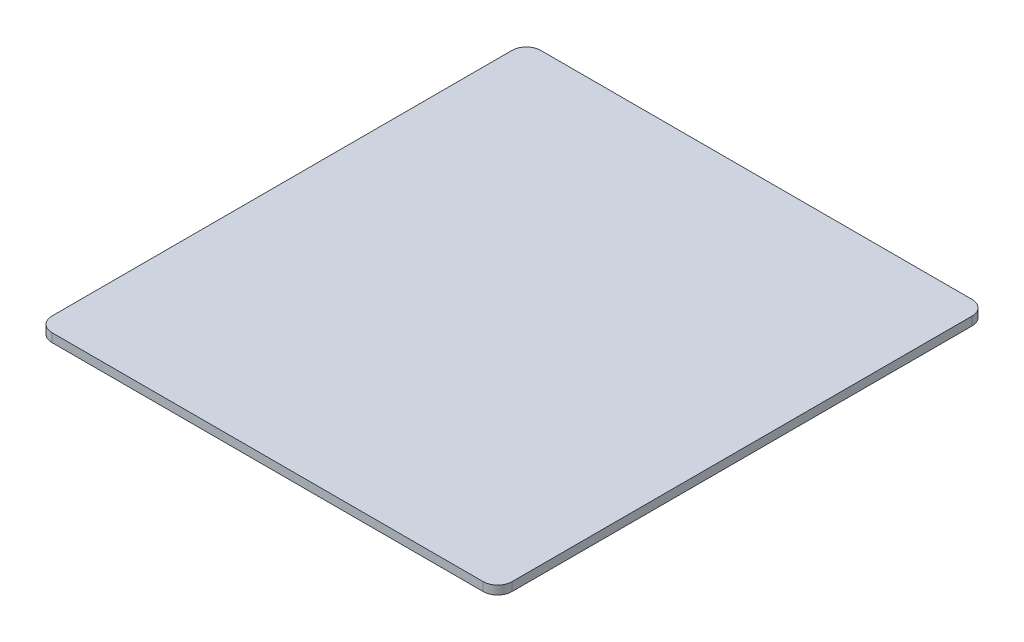
SolidWorks part; units mm, degrees
material "Клен"
ref_plane "Спереди" through (0, 0, 0) normal (0, 0, 1) x (1, 0, 0)
ref_plane "Сверху" through (0, 0, 0) normal (0, 1, 0) x (1, 0, 0)
ref_plane "Справа" through (0, 0, 0) normal (1, 0, 0) x (0, 0, -1)
sketch "Эскиз1" plane through (0, 0, 0) normal (0, 1, 0) x (1, 0, 0)
  line L0 (-199.4521, 0) -> (246.9406, 0) construction
  line L1 (-150, -160) -> (150, -160)
  line L2 (-160, -150) -> (-160, 170)
  line L3 (-150, 180) -> (150, 180)
  line L4 (160, -150) -> (160, 170)
  line L5 (-160, -160) -> (160, 160) construction
  line L6 (-160, 160) -> (160, -160) construction
  line L7 (0, -194.3379) -> (0, 187.7626) construction
  arc A0 (-150, -160) -> (-160, -150) centre (-150, -150) cw
  arc A1 (150, -160) -> (160, -150) centre (150, -150) ccw
  arc A2 (150, 180) -> (160, 170) centre (150, 170) cw
  arc A3 (-160, 170) -> (-150, 180) centre (-150, 170) cw
  point P0 (0, 0)
  point P10 (-612.0811, 16.6389)
  dimension "D2" = 10
  dimension "D1" = 320
  dimension "D3" = 340
extrude "Бобышка-Вытянуть1" add sketch "Эскиз1" along normal blind 6
ref_plane "widht" through (0, 0, 0) normal (-1, 0, 0) x (0, 0, 1)
ref_plane "Плоскость2" through (0, 0, -10) normal (0, 0, -1) x (-1, 0, 0)
